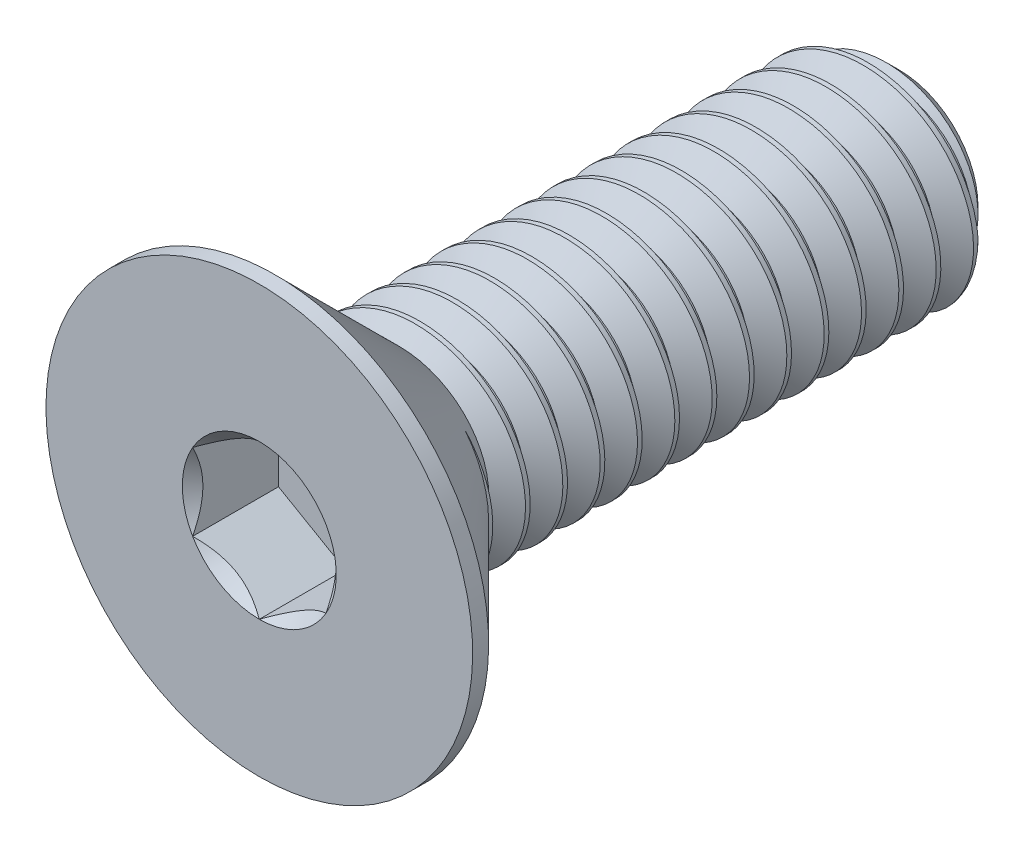
SolidWorks part; units mm, degrees
ref_plane "Front" through (0, 0, 0) normal (0, 0, 1) x (1, 0, 0)
ref_plane "Top" through (0, 0, 0) normal (0, 1, 0) x (1, 0, 0)
ref_plane "Right" through (0, 0, 0) normal (1, 0, 0) x (0, 0, -1)
sketch "Sketch1" plane through (0, 0, 0) normal (1, 0, 0) x (0, 0, -1)
  line L0 (0, 4) -> (0.3, 4) construction
  line L1 (0.3, 4) -> (2.3, 2) construction
  line L2 (0, 2) -> (12, 2)
  line L3 (12, 2) -> (12, 0)
  line L4 (12, 0) -> (0, 0)
  line L5 (0, 0) -> (0, 4) construction
  line L6 (0, 4) -> (0, -4) construction
  line L7 (12, 2) -> (12, -2) construction
  line L8 (0, -4) -> (0.3, -4) construction
  line L9 (0.3, -4) -> (2.3, -2) construction
  line L11 (0, 2) -> (0, 0)
  line L12 (2.3, 2) -> (2.3, 0) construction
revolve "Revolve1" add sketch "Sketch1" angle 360 mid plane about L4
sketch "Sketch3" plane through (0, 0, -12) normal (0, 0, -1) x (-1, 0, 0)
  circle A0 centre (0, 0) radius 2
curve "Helix/Spiral1" pitch 0.7 height 12 radius 2 centre (0, 0, -12) axis (0, 0, 1) start towards (0, 1, 0)
sketch "Sketch2" plane through (0, 0, 0) normal (1, 0, 0) x (0, 0, -1)
  line L0 (12, 2) -> (12.6125, 2)
  line L1 (12.6125, 2) -> (12.35, 1.5453)
  line L2 (12.35, 1.5453) -> (12.2625, 1.5453)
  line L3 (12.2625, 1.5453) -> (12, 2)
  line L4 (12.1312, 1.7727) -> (12.4813, 1.7727) construction
  dimension "D1" = 60
  dimension "D2" = 0.0875
  dimension "D3" = 0.35
chamfer "Chamfer1" distance 0.525 angle 45 1 edges at (0, 2, -12)
sweep "Cut-Sweep1" cut profiles "Sketch2" path "Helix/Spiral1" align with end faces yes
sketch "Sketch7" plane through (0, 0, 0) normal (1, 0, 0) x (0, 0, -1)
  line L0 (0, 4) -> (0.3, 4) construction
  line L1 (0.3, 4) -> (2.3, 2) construction
  line L2 (0, 4) -> (0.3, 4)
  line L3 (0.3, 4) -> (2.3, 2)
  line L4 (2.3, 2) -> (2.3, 0) construction
  line L5 (2.3, 2) -> (2.3, 0)
  line L7 (0, 0) -> (0, 4) construction
  line L8 (0, 0) -> (0, 4)
  line L9 (0, 0) -> (2.3, 0)
  line L10 (4.4, 0) -> (-4.4, 0) construction
revolve "Revolve2" add sketch "Sketch7" angle 360 mid plane about L9
ref_plane "Plane1" through (0, 0, -2.3) normal (0, 0, 1) x (1, 0, 0)
sketch "Sketch8" plane through (0, 0, -2.3) normal (0, 0, 1) x (1, 0, 0)
  circle A0 centre (0, 0) radius 2
extrude "Boss-Extrude1" add sketch "Sketch8" against normal through all draft 45
sketch "Sketch5" plane through (0, 0, 0) normal (0, 0, 1) x (1, 0, 0)
  line L1 (1.25, -0.7217) -> (1.25, 0.7217)
  line L2 (1.25, 0.7217) -> (0, 1.4434)
  line L3 (0, 1.4434) -> (-1.25, 0.7217)
  line L4 (-1.25, 0.7217) -> (-1.25, -0.7217)
  line L5 (-1.25, -0.7217) -> (0, -1.4434)
  line L6 (0, -1.4434) -> (1.25, -0.7217)
  circle A0 centre (0, 0) radius 1.25 construction
  dimension "Hex" = 2.5
extrude "Cut-Extrude2" cut sketch "Sketch5" against normal blind 1.61
sketch "Sketch6" plane through (0, 0, 0) normal (0, 0, 1) x (1, 0, 0)
  circle A0 centre (0, 0) radius 1.4434
extrude "Cut-Extrude3" cut sketch "Sketch6" against normal blind 1.61 draft 45
sketch "Sketch9" [suppressed] plane through (0, 0, -5.5) normal (0, 0, 1) x (1, 0, 0)
  circle A1 centre (0, 0) radius 5
  circle A2 centre (0, 0) radius 5
  point P0 (0, 5)
  dimension "D1" = 0
extrude "Boss-Extrude2" [suppressed] add sketch "Sketch9" against normal offset from surface (18.5 mm away) 26 up to face at (0, 1.475, -12)
fillet "Fillet1" [suppressed] radius 0.4
sketch "Sketch10" plane through (0, 0, 0) normal (1, 0, 0) x (0, 0, -1)
  line L0 (12, 2) -> (12, -2) construction
  point P0 (10.95, -2)
  dimension "D1" = 1.05
equation "\"D3@Helix/Spiral1\" = \"Lg@Sketch1\""
equation "\"D2@Sketch2\" = \"D4@Helix/Spiral1\" * .125"
equation "\"D3@Sketch2\" = \"D4@Helix/Spiral1\" * .5"
equation "\"D1@Chamfer1\" = \"D4@Helix/Spiral1\" * .75"
equation "\"D1@Cut-Extrude2\" = \"Head Ht@Sketch1\" * .7"
equation "\"D1@Sketch10\" = \"D4@Helix/Spiral1\" * 1.5"
equation "\"D1@Cut-Extrude3\" = \"D1@Cut-Extrude2\""
equation "\"D1@Fillet1\" = \"Dia@Sketch1\" * .1"
